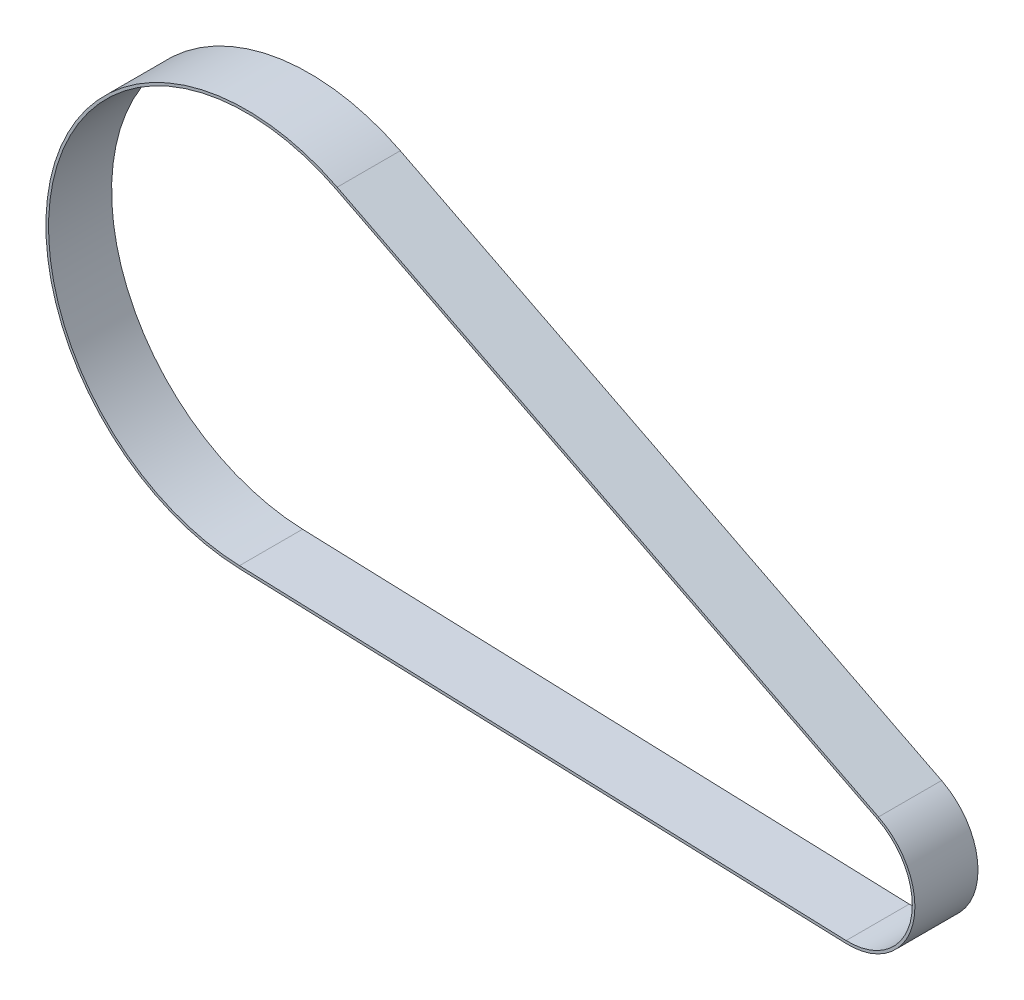
SolidWorks part; units mm, degrees
ref_plane "Front Plane" through (0, 0, 0) normal (0, 0, 1) x (1, 0, 0)
ref_plane "Top Plane" through (0, 0, 0) normal (0, 1, 0) x (1, 0, 0)
ref_plane "Right Plane" through (0, 0, 0) normal (1, 0, 0) x (0, 0, -1)
ref_plane "Plane1" through (0, 0, 25.67) normal (0, 0, 1) x (1, 0, 0)
sketch "Sketch1" plane through (0, 0, 25.67) normal (0, 0, 1) x (1, 0, 0)
  line L2 (60.0035, -51.3694) -> (8.5203, -25.2382)
  line L3 (-0.6617, -60.838) -> (57.038, -62.8672)
  line L4 (60.0035, -51.3694) -> (8.5203, -25.2382)
  line L5 (-0.6617, -60.838) -> (57.038, -62.8672)
  line L6 (60.1166, -51.1465) -> (8.6334, -25.0152)
  line L7 (-0.6704, -61.0878) -> (57.0292, -63.1171)
  arc A2 (57.038, -62.8672) -> (60.0035, -51.3694) centre (57.2517, -56.791) ccw
  arc A3 (8.5203, -25.2382) -> (-0.6617, -60.838) centre (0, -42.0246) ccw
  arc A4 (57.038, -62.8672) -> (60.0035, -51.3694) centre (57.2517, -56.791) ccw
  arc A5 (8.5203, -25.2382) -> (-0.6617, -60.838) centre (0, -42.0246) ccw
  arc A6 (8.6334, -25.0152) -> (-0.6704, -61.0878) centre (0, -42.0246) ccw
  arc A7 (57.0292, -63.1171) -> (60.1166, -51.1465) centre (57.2517, -56.791) ccw
  dimension "D1" = 0
  dimension "D2" = 0.25
extrude "Boss-Extrude1" add sketch "Sketch1" along normal blind 3 and the other way blind 3
